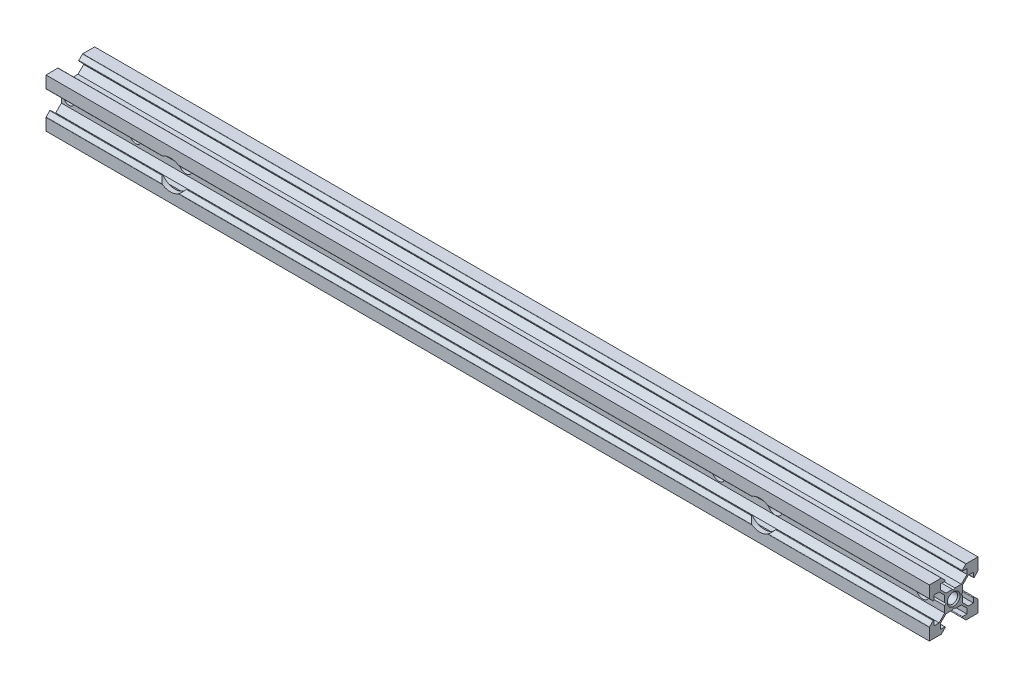
SolidWorks part; units mm, degrees
material "Alloy Steel"
ref_plane "Front Plane" through (0, 0, 0) normal (0, 0, 1) x (1, 0, 0)
ref_plane "Top Plane" through (0, 0, 0) normal (0, 1, 0) x (1, 0, 0)
ref_plane "Right Plane" through (0, 0, 0) normal (1, 0, 0) x (0, 0, -1)
sketch "Sketch2" plane through (0, 0, 0) normal (1, 0, 0) x (0, 0, -1)
  line L0 (0, 2) -> (0, 3) construction
  line L5 (0, 3) -> (-0.5, 3.5)
  line L6 (-0.5, 3.5) -> (-3.01, 3.5)
  line L7 (-3.01, 3.5) -> (-5.2091, 5.6991)
  line L8 (-5.2091, 5.6991) -> (-5.2091, 7.6991)
  line L9 (-5.2091, 7.6991) -> (-3.4791, 7.6991)
  line L10 (-3.4791, 7.6991) -> (-3.4791, 7.8991) construction
  line L11 (-3.4791, 7.8991) -> (-3.3377, 8.0405) construction
  line L12 (-3.3377, 8.0405) -> (-4.7378, 9.4406)
  line L13 (-4.7378, 9.4406) -> (-4.8792, 9.2992) construction
  line L14 (-4.8792, 9.2992) -> (-4.8792, 9.4992) construction
  line L15 (-4.8792, 9.4992) -> (-9.4992, 9.4992)
  line L16 (0, 0) -> (-11.6899, 11.6899) construction
  line L17 (0, 0) -> (-16.8134, 0) construction
  line L18 (-9.4992, 4.8792) -> (-9.4992, 9.4992)
  line L19 (-8.0405, 3.3377) -> (-9.4406, 4.7378)
  line L20 (-7.6991, 5.2091) -> (-7.6991, 3.4791)
  line L21 (-5.6991, 5.2091) -> (-7.6991, 5.2091)
  line L22 (-3.5, 3.01) -> (-5.6991, 5.2091)
  line L23 (-3.5, 0.5) -> (-3.5, 3.01)
  line L24 (-3, 0) -> (-3.5, 0.5)
  line L25 (3, 0) -> (3.5, 0.5)
  line L26 (3.5, 0.5) -> (3.5, 3.01)
  line L27 (3.5, 3.01) -> (5.6991, 5.2091)
  line L28 (5.6991, 5.2091) -> (7.6991, 5.2091)
  line L29 (7.6991, 5.2091) -> (7.6991, 3.4791)
  line L30 (8.0405, 3.3377) -> (9.4406, 4.7378)
  line L31 (9.4992, 4.8792) -> (9.4992, 9.4992)
  line L32 (4.8792, 9.4992) -> (9.4992, 9.4992)
  line L33 (3.3377, 8.0405) -> (4.7378, 9.4406)
  line L34 (5.2091, 7.6991) -> (3.4791, 7.6991)
  line L35 (5.2091, 5.6991) -> (5.2091, 7.6991)
  line L36 (3.01, 3.5) -> (5.2091, 5.6991)
  line L37 (0.5, 3.5) -> (3.01, 3.5)
  line L38 (0, 3) -> (0.5, 3.5)
  line L39 (2, 0) -> (3, 0) construction
  line L40 (7.6991, 3.4791) -> (7.8991, 3.4791) construction
  line L41 (7.8991, 3.4791) -> (8.0405, 3.3377) construction
  line L42 (9.4406, 4.7378) -> (9.2992, 4.8792) construction
  line L43 (9.2992, 4.8792) -> (9.4992, 4.8792) construction
  line L44 (0, 0) -> (11.6899, 11.6899) construction
  line L45 (0, 0) -> (0, 16.8134) construction
  line L46 (0, -3) -> (0.5, -3.5)
  line L47 (0.5, -3.5) -> (3.01, -3.5)
  line L48 (3.01, -3.5) -> (5.2091, -5.6991)
  line L49 (5.2091, -5.6991) -> (5.2091, -7.6991)
  line L50 (5.2091, -7.6991) -> (3.4791, -7.6991)
  line L51 (3.3377, -8.0405) -> (4.7378, -9.4406)
  line L52 (4.8792, -9.4992) -> (9.4992, -9.4992)
  line L53 (9.4992, -4.8792) -> (9.4992, -9.4992)
  line L54 (8.0405, -3.3377) -> (9.4406, -4.7378)
  line L55 (7.6991, -5.2091) -> (7.6991, -3.4791)
  line L56 (5.6991, -5.2091) -> (7.6991, -5.2091)
  line L57 (3.5, -3.01) -> (5.6991, -5.2091)
  line L58 (3.5, -0.5) -> (3.5, -3.01)
  line L59 (3, 0) -> (3.5, -0.5)
  line L60 (0, -2) -> (0, -3) construction
  line L61 (3.4791, -7.6991) -> (3.4791, -7.8991) construction
  line L62 (3.4791, -7.8991) -> (3.3377, -8.0405) construction
  line L63 (4.7378, -9.4406) -> (4.8792, -9.2992) construction
  line L64 (4.8792, -9.2992) -> (4.8792, -9.4992) construction
  line L65 (0, 0) -> (11.6899, -11.6899) construction
  line L66 (0, 0) -> (16.8134, 0) construction
  line L67 (-3, 0) -> (-3.5, -0.5)
  line L68 (-3.5, -0.5) -> (-3.5, -3.01)
  line L69 (-3.5, -3.01) -> (-5.6991, -5.2091)
  line L70 (-5.6991, -5.2091) -> (-7.6991, -5.2091)
  line L71 (-7.6991, -5.2091) -> (-7.6991, -3.4791)
  line L72 (-8.0405, -3.3377) -> (-9.4406, -4.7378)
  line L73 (-9.4992, -4.8792) -> (-9.4992, -9.4992)
  line L74 (-4.8792, -9.4992) -> (-9.4992, -9.4992)
  line L75 (-3.3377, -8.0405) -> (-4.7378, -9.4406)
  line L76 (-5.2091, -7.6991) -> (-3.4791, -7.6991)
  line L77 (-5.2091, -5.6991) -> (-5.2091, -7.6991)
  line L78 (-3.01, -3.5) -> (-5.2091, -5.6991)
  line L79 (-0.5, -3.5) -> (-3.01, -3.5)
  line L80 (0, -3) -> (-0.5, -3.5)
  line L81 (-2, 0) -> (-3, 0) construction
  line L82 (-7.6991, -3.4791) -> (-7.8991, -3.4791) construction
  line L83 (-7.8991, -3.4791) -> (-8.0405, -3.3377) construction
  line L84 (-9.4406, -4.7378) -> (-9.2992, -4.8792) construction
  line L85 (-9.2992, -4.8792) -> (-9.4992, -4.8792) construction
  line L86 (0, 0) -> (-11.6899, -11.6899) construction
  line L87 (0, 0) -> (0, -16.8134) construction
  circle A0 centre (0, 0) radius 2
  arc A1 (-3.3377, 8.0405) -> (-3.4791, 7.6991) centre (-3.4791, 7.8991) cw
  arc A2 (-4.7378, 9.4406) -> (-4.8792, 9.4992) centre (-4.8792, 9.2992) ccw
  arc A3 (-9.4406, 4.7378) -> (-9.4992, 4.8792) centre (-9.2992, 4.8792) cw
  arc A4 (-8.0405, 3.3377) -> (-7.6991, 3.4791) centre (-7.8991, 3.4791) ccw
  arc A5 (8.0405, 3.3377) -> (7.6991, 3.4791) centre (7.8991, 3.4791) cw
  arc A6 (9.4406, 4.7378) -> (9.4992, 4.8792) centre (9.2992, 4.8792) ccw
  arc A7 (4.7378, 9.4406) -> (4.8792, 9.4992) centre (4.8792, 9.2992) cw
  arc A8 (3.3377, 8.0405) -> (3.4791, 7.6991) centre (3.4791, 7.8991) ccw
  arc A9 (3.3377, -8.0405) -> (3.4791, -7.6991) centre (3.4791, -7.8991) cw
  arc A10 (4.7378, -9.4406) -> (4.8792, -9.4992) centre (4.8792, -9.2992) ccw
  arc A11 (9.4406, -4.7378) -> (9.4992, -4.8792) centre (9.2992, -4.8792) cw
  arc A12 (8.0405, -3.3377) -> (7.6991, -3.4791) centre (7.8991, -3.4791) ccw
  arc A13 (-8.0405, -3.3377) -> (-7.6991, -3.4791) centre (-7.8991, -3.4791) cw
  arc A14 (-9.4406, -4.7378) -> (-9.4992, -4.8792) centre (-9.2992, -4.8792) ccw
  arc A15 (-4.7378, -9.4406) -> (-4.8792, -9.4992) centre (-4.8792, -9.2992) cw
  arc A16 (-3.3377, -8.0405) -> (-3.4791, -7.6991) centre (-3.4791, -7.8991) ccw
  point P0 (0, 0)
  point P22 (0, 0)
  point P64 (0, 0)
  point P93 (0, 0)
  point P122 (0, 0)
  dimension "D1" = 4
  dimension "D13" = 0.2
  dimension "D18" = 0.2
  dimension "D2" = 1
  dimension "D3" = 0.5
  dimension "D4" = 135
  dimension "D5" = 2.51
  dimension "D6" = 135
  dimension "D7" = 3.11
  dimension "D8" = 2
  dimension "D9" = 1.73
  dimension "D10" = 0.2
  dimension "D11" = 0.2
  dimension "D12" = 135
  dimension "D14" = 1.98
  dimension "D15" = 90
  dimension "D16" = 0.2
  dimension "D17" = 0.2
  dimension "D19" = 4
  dimension "D20" = 45
extrude "Main Body" add sketch "Sketch2" along normal blind 172.5 and the other way blind 172.5 contours L75 A16 L76 L77 L78 L79 L80 L46 L47 L48 L49 L50 A9 L51 A10 L52 L53 A11 L54 A12 L55 L56 L57 L58 L59 L25 L26 L27 L28 L29 A5 L30 A6 L31 L32 A7 L33 A8 L34 L35 L36 L37 L38 L5 L6 L7 L8 L9 A1 L12 A2 region at (0, 3.06, -0.44)
chamfer "Chamfer1" distance 0.5 angle 45 1 edges at (172.5, 0, -2)
chamfer "Chamfer2" distance 0.5 angle 45 1 edges at (-172.5, 0, -2)
sketch "Sketch3" plane through (0, 0, 0) normal (0, 0, 1) x (1, 0, 0)
  line L0 (-172.5, 0) -> (172.5, 0) construction
  line L1 (172.5, -0.5) -> (172.5, -3.01) construction
  line L2 (-172.5, -0.5) -> (-172.5, -3.01) construction
  line L3 (-172.5, -4.8792) -> (-172.5, -9.4992) construction
  circle A0 centre (163.9, 0) radius 2.55
  circle A1 centre (106.3, 0) radius 2.95
  circle A2 centre (84.2, 0) radius 2.55
  circle A3 centre (-169.5, 0) radius 2.25
  circle A4 centre (-143.5, 0) radius 2.25
  circle A5 centre (-123.9, 0) radius 2.6
  dimension "D4" = 5.1
  dimension "D5" = 5.9
  dimension "D6" = 5.1
  dimension "D10" = 4.5
  dimension "D11" = 4.5
  dimension "D12" = 5.2
  dimension "D1" = 8.6
  dimension "D2" = 66.2
  dimension "D3" = 88.3
  dimension "D7" = 48.6
  dimension "D8" = 29
  dimension "D9" = 3
sketch "Sketch4" plane through (0, 0, 0) normal (1, 0, 0) x (0, 0, -1)
  line L0 (-0.5, 3.5) -> (0.5, 3.5)
  line L1 (0.5, 3.5) -> (0.5, 2.9712)
  line L2 (0.5, 2.9712) -> (-0.5, 2.9712)
  line L3 (-0.5, 2.9712) -> (-0.5, 3.5)
  line L4 (2.9712, 0.5) -> (3.5, 0.5)
  line L5 (3.5, 0.5) -> (3.5, -0.5)
  line L6 (3.5, -0.5) -> (2.9712, -0.5)
  line L7 (2.9712, -0.5) -> (2.9712, 0.5)
  line L8 (0.5, -2.9712) -> (0.5, -3.5)
  line L9 (0.5, -3.5) -> (-0.5, -3.5)
  line L10 (-0.5, -3.5) -> (-0.5, -2.9712)
  line L11 (-0.5, -2.9712) -> (0.5, -2.9712)
  line L12 (-2.9712, -0.5) -> (-3.5, -0.5)
  line L13 (-3.5, -0.5) -> (-3.5, 0.5)
  line L14 (-3.5, 0.5) -> (-2.9712, 0.5)
  line L15 (-2.9712, 0.5) -> (-2.9712, -0.5)
  point P21 (0, 0)
  dimension "D1" = 1
  dimension "D2" = 0.5288
  dimension "D3" = 4
extrude "Base Fix" add sketch "Sketch4" along normal up to surface and the other way up to surface up to face at (172.5, 0, -2.5) other way up to face at (-172.5, 0, -2.5)
sketch "Sketch8" plane through (172.5, 0, 0) normal (1, 0, 0) x (0, 0, -1)
  line L0 (0, 3.5) -> (0, 3) construction
  line L1 (-3.01, 3.5) -> (3.01, 3.5) construction
  line L2 (0, 3) -> (0.5, 3.5)
  line L3 (0, 3) -> (-0.5, 3.5)
  line L4 (-0.5, 3.5) -> (0.5, 3.5)
  line L5 (3.5, 0.5) -> (3.5, -0.5)
  line L6 (3, 0) -> (3.5, -0.5)
  line L7 (3, 0) -> (3.5, 0.5)
  line L8 (0.5, -3.5) -> (-0.5, -3.5)
  line L9 (0, -3) -> (-0.5, -3.5)
  line L10 (0, -3) -> (0.5, -3.5)
  line L11 (-3.5, -0.5) -> (-3.5, 0.5)
  line L12 (-3, 0) -> (-3.5, 0.5)
  line L13 (-3, 0) -> (-3.5, -0.5)
  line L14 (-3.5, -3.01) -> (-3.5, 3.01) construction
  point P19 (0, 0)
  dimension "D1" = 45
  dimension "D2" = 0.5
  dimension "D3" = 4
extrude "Screw Holes" cut sketch "Sketch3" against normal through all both and the other way through all
extrude "Rail Cut" cut sketch "Sketch8" against normal through all contours L13 L12 L11 | L10 L8 L9 | L2 L4 L3 | L5 L6 L7 region at (172.5, 0, 3.3333)
sketch "Sketch11" plane through (0, 0, 9.4992) normal (0, 0, 1) x (1, 0, 0)
  circle A0 centre (106.3, 0) radius 5.75
  circle A1 centre (-123.9, 0) radius 5.75
  dimension "D1" = 11.5
  dimension "D2" = 11.5
extrude "Cut-Extrude19" cut sketch "Sketch11" against normal up to surface (1.8001 mm away) up to face at (0, 4.3441, 7.6991)
